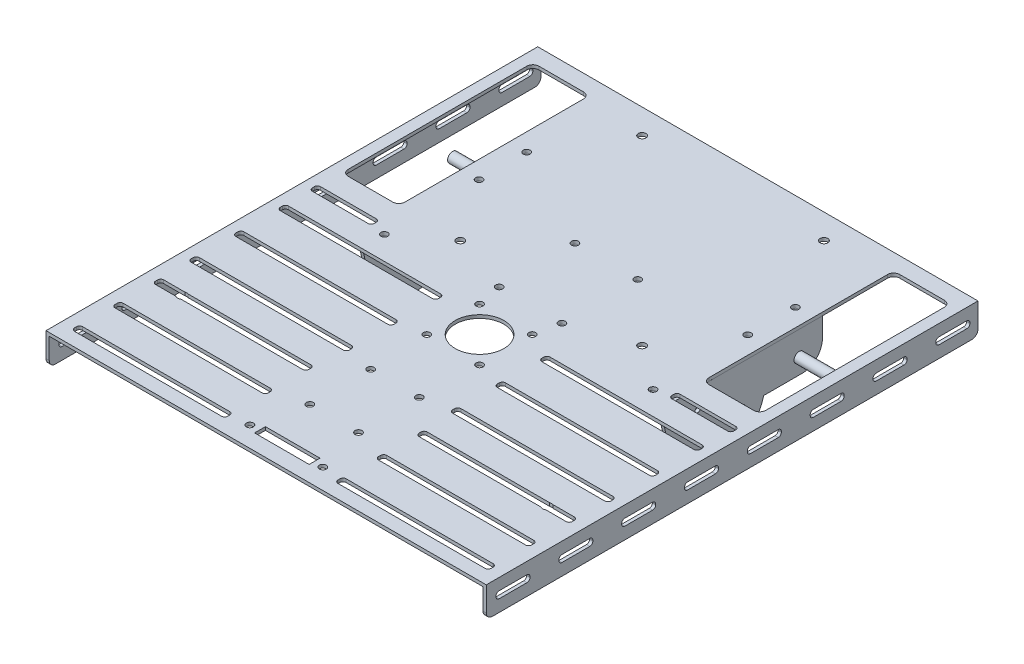
SolidWorks part; units mm, degrees
ref_plane "Front Plane" through (0, 0, 0) normal (0, 0, 1) x (1, 0, 0)
ref_plane "Top Plane" through (0, 0, 0) normal (0, 1, 0) x (1, 0, 0)
ref_plane "Right Plane" through (0, 0, 0) normal (1, 0, 0) x (0, 0, -1)
sketch "Sketch2" plane through (0, 0, 0) normal (0, 1, 0) x (1, 0, 0)
  line L7 (-172.2662, -88.2141) -> (41.7338, -88.2141)
  line L48 (-168.2662, 146.3841) -> (-140.2662, 146.3841)
  line L49 (-168.2662, 146.3841) -> (-168.2662, 52.2603)
  line L50 (-168.2662, 52.2603) -> (-140.2662, 52.2603)
  line L51 (-140.2662, 146.3841) -> (-140.2662, 52.2603)
  line L72 (41.7338, 154.3841) -> (-172.2662, 154.3841)
  line L75 (-65.2662, 154.3841) -> (-65.2662, -88.2141) construction
  line L76 (41.7338, -88.2141) -> (41.7338, 154.3841)
  line L77 (9.7338, 146.3841) -> (9.7338, 52.2603)
  line L78 (37.7338, 52.2603) -> (9.7338, 52.2603)
  line L79 (-172.2662, -88.2141) -> (-172.2662, 154.3841)
  line L80 (37.7338, 146.3841) -> (37.7338, 52.2603)
  line L81 (37.7338, 146.3841) -> (9.7338, 146.3841)
  point P2 (-154.2662, 146.3841)
  dimension "D1" = 8
  dimension "D3" = 4
  dimension "D6" = 107
  dimension "D9" = 28
extrude "Boss-Extrude1" add sketch "Sketch2" along normal blind 1.6
ref_plane "Plane3" through (-65.2662, 0, 0) normal (-1, 0, 0) x (0, 0, 1)
sketch "Sketch4" plane through (0, 0, 0) normal (0, -1, 0) x (1, 0, 0)
  line L5 (-172.2662, 15.9553) -> (41.7338, 15.9553) construction
  line L6 (-172.2662, -154.3841) -> (-172.2662, 88.2141) construction
  line L7 (41.7338, 88.2141) -> (41.7338, -154.3841) construction
  point P6 (-65.2662, 15.9553)
  line B0 (-140.2673, -111.2297) -> (-140.2673, -31.6718)
  line B1 (-140.2673, -111.2297) -> (-127.4267, -111.2297)
  line B2 (-140.2673, -31.6718) -> (-127.4299, -31.6718)
  line B3 (-76.7662, -37.9313) -> (-76.7662, -84.2325)
  line B4 (-76.7662, -37.9313) -> (-85.1807, -37.9313)
  line B5 (-76.7662, -84.2325) -> (-85.1807, -84.2325)
  line B6 (-122.4299, -36.6718) -> (-122.4299, -60.4336)
  line B7 (-122.4299, -60.4336) -> (-85.1807, -60.4336)
  line B8 (-85.1807, -60.4336) -> (-85.1807, -37.9313)
  line B9 (-85.1807, -84.2325) -> (-85.1807, -67.1203)
  line B10 (-85.1807, -67.1203) -> (-122.4267, -67.1203)
  line B11 (-122.4267, -67.1203) -> (-122.4267, -106.2297)
  arc B12 (-127.4299, -31.6718) -> (-122.4299, -36.6718) centre (-127.4299, -36.6718) cw
  arc B13 (-127.4267, -111.2297) -> (-122.4267, -106.2297) centre (-127.4267, -106.2297) ccw
  dimension "D1" = 11.5
sketch_block_instance "Block1-1"
sketch_block "Block1" parameters "D1"=5
extrude "Boss-Extrude3" add sketch "Sketch4" along normal blind 1.6129 separate body
sketch "Sketch6" plane through (-140.2673, 113.8349, 0) normal (1, 0, 0) x (0, -1, 0)
  line L1 (113.8349, 31.6718) -> (113.8349, 111.2297)
  line L7 (123.4041, 111.2297) -> (113.8349, 111.2297)
  line L8 (113.8349, 52.2603) -> (113.8349, 146.3841) construction
  line L10 (115.4478, 111.2297) -> (113.8349, 111.2297) construction
  line L11 (133.4041, 101.2297) -> (133.4041, 82.2567)
  line L13 (132.4365, 35.6062) -> (115.4478, 31.6718)
  line L14 (115.4478, 31.6718) -> (113.8349, 31.6718)
  circle A2 centre (133.4041, 71.8386) radius 1.27
  circle A4 centre (133.4041, 49.6644) radius 3
  circle A5 centre (125.8349, 99.7882) radius 2.55
  circle A6 centre (123.1933, 49.6644) radius 1.27
  circle A8 centre (143.6149, 49.6644) radius 1.27
  arc A10 (133.4041, 82.2567) -> (132.4365, 35.6062) centre (127.5185, 59.0435) cw
  arc A11 (133.4041, 101.2297) -> (123.4041, 111.2297) centre (123.4041, 101.2297) ccw
  line M25 (113.8349, 31.6718) -> (113.8349, 111.2297)
  line M26 (113.8349, 111.2297) -> (115.4478, 111.2297)
  line M27 (115.4478, 111.2297) -> (115.4478, 31.6718)
  line M28 (115.4478, 31.6718) -> (113.8349, 31.6718)
  dimension "D1" = 5.1
  dimension "D4" = 6
  dimension "D5" = 10
  dimension "D2" = 12
extrude "Boss-Extrude4" add sketch "Sketch6" along normal blind 1.6129 contours M28 M25 M26 M27 | M27 | A6 A2 A4 A8 region at (-140.2673, -0.8064, -71.4508) region at (-140.2673, -15.5641, -67.9069)
sketch "Sketch7" plane through (0, 0, 0) normal (0, -1, 0) x (1, 0, 0)
  line L0 (-172.2662, 88.2141) -> (41.7338, 88.2141) construction
  line L1 (-65.2662, -5.0799) -> (-65.2662, -29.0799)
  line L48 (-65.2662, -1159.7859) -> (-65.2662, 48840.2141) construction
  line L49 (41.7338, -154.3841) -> (-172.2662, -154.3841) construction
  line L50 (-65.2662, 80.4578) -> (-65.2662, 75.1009)
  line L51 (-65.2662, 80.4578) -> (-78.7298, 80.4578)
  line L52 (-65.2662, 75.1009) -> (-78.7298, 75.1009)
  line L53 (-78.7298, 80.4578) -> (-78.7298, 75.1009)
  circle A0 centre (-131.5463, -83.1098) radius 1.7
  circle A1 centre (-131.5463, -36.3977) radius 1.7
  circle A2 centre (-80.7521, -42.2194) radius 1.7
  circle A3 centre (-80.7521, -79.6224) radius 1.7
  circle A4 centre (-131.5463, -106.6172) radius 1.7
  circle A5 centre (-110.1162, -52.4299) radius 1.9
  circle A6 centre (-110.1162, -142.1299) radius 1.9
  circle A7 centre (-155.2662, 39.5701) radius 2.25
  circle A8 centre (-78.2662, -4.0799) radius 1.7
  circle A9 centre (-78.2662, -30.0799) radius 1.7
  arc A11 (-65.2662, -5.0799) -> (-65.2662, -29.0799) centre (-65.2662, -17.0799) ccw
  circle A12 centre (-83.2662, 78.2141) radius 1.7
  circle A13 centre (-77.2662, 24.6349) radius 1.7
  circle A14 centre (-77.2662, 54.6349) radius 1.7
  point P38 (-65.2662, -154.3841)
  dimension "D3" = 3.4
  dimension "D4" = 3.4
  dimension "D5" = 3.4
  dimension "D6" = 3.4
  dimension "D1" = 3.4
  dimension "D2" = 3.8
  dimension "D8" = 3.8
  dimension "D9" = 4.5
  dimension "D12" = 3.4
  dimension "D13" = 3.4
  dimension "D14" = 12
  dimension "D20" = 3.4
  dimension "D23" = 3.4
  dimension "D24" = 3.4
  dimension "D22" = 10
  dimension "D25" = 30
  dimension "D15" = 13
  dimension "D19" = 12
  dimension "D21" = 18
  dimension "D11" = 89.7
  dimension "D17" = 13
  dimension "D18" = 26
  dimension "D7" = 92
  dimension "D16" = 44.85
  dimension "D10" = 90
  dimension "D28" = 35.35
extrude "Cut-Extrude1" cut sketch "Sketch7" against normal blind 10 and the other way blind 10
mirror "Mirror1" about plane through (-65.2662, 0, 0) normal (-1, 0, 0) of bodies 157 158 103
mirror "Mirror2" about plane through (-65.2662, 0, 0) normal (-1, 0, 0) of "Cut-Extrude1"
sketch "Sketch9" plane through (-140.2662, 0, 0) normal (1, 0, 0) x (0, 0, -1)
  circle A0 centre (99.7882, -12) radius 2.5
extrude "Boss-Extrude6" add sketch "Sketch9" along normal blind 169 and the other way blind 21 separate body
sketch "Sketch11" plane through (0, 1.6, 0) normal (0, 1, 0) x (1, 0, 0)
  line L0 (-172.2662, 154.3841) -> (-172.2662, -88.2141)
  line L1 (-172.2662, 154.3841) -> (-173.8662, 154.3841)
  line L2 (-172.2662, -88.2141) -> (-173.8662, -88.2141)
  line L3 (-173.8662, 154.3841) -> (-173.8662, -88.2141)
  line L4 (41.7338, 154.3841) -> (41.7338, -88.2141)
  line L5 (41.7338, 154.3841) -> (43.3338, 154.3841)
  line L6 (41.7338, -88.2141) -> (43.3338, -88.2141)
  line L7 (43.3338, 154.3841) -> (43.3338, -88.2141)
  dimension "D1" = 1.6
  dimension "D2" = 1.6
extrude "Boss-Extrude7" add sketch "Sketch11" against normal blind 15
sketch "Sketch12" plane through (0, 1.6, 0) normal (0, 1, 0) x (1, 0, 0)
  line L12 (-65.2662, -1088.2141) -> (-65.2662, 48911.7859) construction
  line L13 (-173.8662, -88.2141) -> (43.3338, -88.2141) construction
  line L78 (-167.2842, 24.8362) -> (-92.2703, 24.8362)
  line L79 (-168.7842, 23.3362) -> (-168.7842, 22.3362)
  line L80 (-90.7703, 23.3362) -> (-90.7703, 22.3362)
  line L81 (-167.2842, 20.8362) -> (-92.2703, 20.8362)
  line L98 (-166.5277, -37.4749) -> (-93.977, -37.4749)
  line L99 (-168.0277, -38.9749) -> (-168.0277, -39.9749)
  line L100 (-92.477, -38.9749) -> (-92.477, -39.9749)
  line L101 (-166.5277, -41.4749) -> (-93.977, -41.4749)
  line L134 (-167.2842, -1.1638) -> (-92.2703, -1.1638)
  line L135 (-90.7703, 1.3362) -> (-90.7703, 0.3362)
  line L136 (-167.2842, 2.8362) -> (-92.2703, 2.8362)
  line L137 (-168.7842, 1.3362) -> (-168.7842, 0.3362)
  line L138 (-167.2842, -23.1638) -> (-92.2703, -23.1638)
  line L139 (-90.7703, -20.6638) -> (-90.7703, -21.6638)
  line L140 (-167.2842, -19.1638) -> (-92.2703, -19.1638)
  line L141 (-168.7842, -20.6638) -> (-168.7842, -21.6638)
  line L142 (-166.5277, -57.4749) -> (-93.977, -57.4749)
  line L143 (-168.0277, -58.9749) -> (-168.0277, -59.9749)
  line L144 (-92.477, -58.9749) -> (-92.477, -59.9749)
  line L145 (-166.5277, -61.4749) -> (-93.977, -61.4749)
  line L146 (-166.5277, -77.4749) -> (-93.977, -77.4749)
  line L147 (-168.0277, -78.9749) -> (-168.0277, -79.9749)
  line L148 (-92.477, -78.9749) -> (-92.477, -79.9749)
  line L149 (-166.5277, -81.4749) -> (-93.977, -81.4749)
  line L150 (35.9953, -81.4749) -> (-36.5554, -81.4749)
  line L151 (-38.0554, -78.9749) -> (-38.0554, -79.9749)
  line L152 (37.4953, -78.9749) -> (37.4953, -79.9749)
  line L153 (35.9953, -77.4749) -> (-36.5554, -77.4749)
  line L154 (35.9953, -61.4749) -> (-36.5554, -61.4749)
  line L155 (-38.0554, -58.9749) -> (-38.0554, -59.9749)
  line L156 (37.4953, -58.9749) -> (37.4953, -59.9749)
  line L157 (35.9953, -57.4749) -> (-36.5554, -57.4749)
  line L158 (38.2518, -20.6638) -> (38.2518, -21.6638)
  line L159 (36.7518, -19.1638) -> (-38.2621, -19.1638)
  line L160 (-39.7621, -20.6638) -> (-39.7621, -21.6638)
  line L161 (36.7518, -23.1638) -> (-38.2621, -23.1638)
  line L162 (38.2518, 1.3362) -> (38.2518, 0.3362)
  line L163 (36.7518, 2.8362) -> (-38.2621, 2.8362)
  line L164 (-39.7621, 1.3362) -> (-39.7621, 0.3362)
  line L165 (36.7518, -1.1638) -> (-38.2621, -1.1638)
  line L166 (35.9953, -41.4749) -> (-36.5554, -41.4749)
  line L167 (-38.0554, -38.9749) -> (-38.0554, -39.9749)
  line L168 (37.4953, -38.9749) -> (37.4953, -39.9749)
  line L169 (35.9953, -37.4749) -> (-36.5554, -37.4749)
  line L170 (36.7518, 20.8362) -> (-38.2621, 20.8362)
  line L171 (-39.7621, 23.3362) -> (-39.7621, 22.3362)
  line L172 (38.2518, 23.3362) -> (38.2518, 22.3362)
  line L173 (36.7518, 24.8362) -> (-38.2621, 24.8362)
  line L174 (-167.6958, 41.0358) -> (-140.217, 41.0358)
  line L175 (-169.1958, 39.5358) -> (-169.1958, 38.5358)
  line L176 (-138.717, 39.5358) -> (-138.717, 38.5358)
  line L177 (-167.6958, 37.0358) -> (-140.217, 37.0358)
  line L178 (38.6634, 39.5358) -> (38.6634, 38.5358)
  line L179 (37.1634, 41.0358) -> (9.6846, 41.0358)
  line L180 (8.1846, 39.5358) -> (8.1846, 38.5358)
  line L181 (37.1634, 37.0358) -> (9.6846, 37.0358)
  arc A0 (-92.2703, 24.8362) -> (-90.7703, 23.3362) centre (-92.2703, 23.3362) cw
  arc A1 (-90.7703, 22.3362) -> (-92.2703, 20.8362) centre (-92.2703, 22.3362) cw
  arc A2 (-168.7842, 22.3362) -> (-167.2842, 20.8362) centre (-167.2842, 22.3362) ccw
  arc A3 (-168.7842, 23.3362) -> (-167.2842, 24.8362) centre (-167.2842, 23.3362) cw
  arc A4 (-90.7703, 0.3362) -> (-92.2703, -1.1638) centre (-92.2703, 0.3362) cw
  arc A5 (-92.2703, 2.8362) -> (-90.7703, 1.3362) centre (-92.2703, 1.3362) cw
  arc A6 (-168.7842, 1.3362) -> (-167.2842, 2.8362) centre (-167.2842, 1.3362) cw
  arc A7 (-168.7842, 0.3362) -> (-167.2842, -1.1638) centre (-167.2842, 0.3362) ccw
  arc A8 (-90.7703, -21.6638) -> (-92.2703, -23.1638) centre (-92.2703, -21.6638) cw
  arc A9 (-92.2703, -19.1638) -> (-90.7703, -20.6638) centre (-92.2703, -20.6638) cw
  arc A10 (-168.7842, -20.6638) -> (-167.2842, -19.1638) centre (-167.2842, -20.6638) cw
  arc A11 (-168.7842, -21.6638) -> (-167.2842, -23.1638) centre (-167.2842, -21.6638) ccw
  arc A12 (-93.977, -37.4749) -> (-92.477, -38.9749) centre (-93.977, -38.9749) cw
  arc A13 (-92.477, -39.9749) -> (-93.977, -41.4749) centre (-93.977, -39.9749) cw
  arc A14 (-168.0277, -39.9749) -> (-166.5277, -41.4749) centre (-166.5277, -39.9749) ccw
  arc A15 (-168.0277, -38.9749) -> (-166.5277, -37.4749) centre (-166.5277, -38.9749) cw
  arc A32 (-93.977, -57.4749) -> (-92.477, -58.9749) centre (-93.977, -58.9749) cw
  arc A33 (-92.477, -59.9749) -> (-93.977, -61.4749) centre (-93.977, -59.9749) cw
  arc A34 (-168.0277, -59.9749) -> (-166.5277, -61.4749) centre (-166.5277, -59.9749) ccw
  arc A35 (-168.0277, -58.9749) -> (-166.5277, -57.4749) centre (-166.5277, -58.9749) cw
  arc A36 (-93.977, -77.4749) -> (-92.477, -78.9749) centre (-93.977, -78.9749) cw
  arc A37 (-92.477, -79.9749) -> (-93.977, -81.4749) centre (-93.977, -79.9749) cw
  arc A38 (-168.0277, -79.9749) -> (-166.5277, -81.4749) centre (-166.5277, -79.9749) ccw
  arc A39 (-168.0277, -78.9749) -> (-166.5277, -77.4749) centre (-166.5277, -78.9749) cw
  arc A40 (37.4953, -78.9749) -> (35.9953, -77.4749) centre (35.9953, -78.9749) ccw
  arc A41 (37.4953, -79.9749) -> (35.9953, -81.4749) centre (35.9953, -79.9749) cw
  arc A42 (-38.0554, -79.9749) -> (-36.5554, -81.4749) centre (-36.5554, -79.9749) ccw
  arc A43 (-36.5554, -77.4749) -> (-38.0554, -78.9749) centre (-36.5554, -78.9749) ccw
  arc A44 (37.4953, -58.9749) -> (35.9953, -57.4749) centre (35.9953, -58.9749) ccw
  arc A45 (37.4953, -59.9749) -> (35.9953, -61.4749) centre (35.9953, -59.9749) cw
  arc A46 (-38.0554, -59.9749) -> (-36.5554, -61.4749) centre (-36.5554, -59.9749) ccw
  arc A47 (-36.5554, -57.4749) -> (-38.0554, -58.9749) centre (-36.5554, -58.9749) ccw
  arc A48 (37.4953, -38.9749) -> (35.9953, -37.4749) centre (35.9953, -38.9749) ccw
  arc A49 (37.4953, -39.9749) -> (35.9953, -41.4749) centre (35.9953, -39.9749) cw
  arc A50 (-38.0554, -39.9749) -> (-36.5554, -41.4749) centre (-36.5554, -39.9749) ccw
  arc A51 (-36.5554, -37.4749) -> (-38.0554, -38.9749) centre (-36.5554, -38.9749) ccw
  arc A52 (38.2518, -21.6638) -> (36.7518, -23.1638) centre (36.7518, -21.6638) cw
  arc A53 (38.2518, -20.6638) -> (36.7518, -19.1638) centre (36.7518, -20.6638) ccw
  arc A54 (-38.2621, -19.1638) -> (-39.7621, -20.6638) centre (-38.2621, -20.6638) ccw
  arc A55 (-39.7621, -21.6638) -> (-38.2621, -23.1638) centre (-38.2621, -21.6638) ccw
  arc A56 (38.2518, 0.3362) -> (36.7518, -1.1638) centre (36.7518, 0.3362) cw
  arc A57 (38.2518, 1.3362) -> (36.7518, 2.8362) centre (36.7518, 1.3362) ccw
  arc A58 (-38.2621, 2.8362) -> (-39.7621, 1.3362) centre (-38.2621, 1.3362) ccw
  arc A59 (-39.7621, 0.3362) -> (-38.2621, -1.1638) centre (-38.2621, 0.3362) ccw
  arc A60 (38.2518, 23.3362) -> (36.7518, 24.8362) centre (36.7518, 23.3362) ccw
  arc A61 (38.2518, 22.3362) -> (36.7518, 20.8362) centre (36.7518, 22.3362) cw
  arc A62 (-39.7621, 22.3362) -> (-38.2621, 20.8362) centre (-38.2621, 22.3362) ccw
  arc A63 (-38.2621, 24.8362) -> (-39.7621, 23.3362) centre (-38.2621, 23.3362) ccw
  arc A64 (-140.217, 41.0358) -> (-138.717, 39.5358) centre (-140.217, 39.5358) cw
  arc A65 (-138.717, 38.5358) -> (-140.217, 37.0358) centre (-140.217, 38.5358) cw
  arc A66 (-169.1958, 38.5358) -> (-167.6958, 37.0358) centre (-167.6958, 38.5358) ccw
  arc A67 (-169.1958, 39.5358) -> (-167.6958, 41.0358) centre (-167.6958, 39.5358) cw
  arc A68 (38.6634, 38.5358) -> (37.1634, 37.0358) centre (37.1634, 38.5358) cw
  arc A69 (38.6634, 39.5358) -> (37.1634, 41.0358) centre (37.1634, 39.5358) ccw
  arc A70 (9.6846, 41.0358) -> (8.1846, 39.5358) centre (9.6846, 39.5358) ccw
  arc A71 (8.1846, 38.5358) -> (9.6846, 37.0358) centre (9.6846, 38.5358) ccw
  point P41 (-65.2662, -88.2141)
  point P42 (-92.477, -37.4749)
  point P45 (-92.477, -41.4749)
  point P48 (-168.0277, -41.4749)
  point P51 (-168.0277, -37.4749)
  point P55 (-90.7703, 24.8362)
  point P58 (-90.7703, 20.8362)
  point P61 (-168.7842, 20.8362)
  point P64 (-168.7842, 24.8362)
  point P157 (38.2518, 24.8362)
  point P158 (38.2518, 20.8362)
  point P159 (-39.7621, 20.8362)
  point P160 (-39.7621, 24.8362)
  point P161 (37.4953, -37.4749)
  point P162 (37.4953, -41.4749)
  point P163 (-38.0554, -41.4749)
  point P164 (-38.0554, -37.4749)
  dimension "D1" = 1.5
  dimension "D3" = 1.5
  dimension "D2" = 3
  dimension "D4" = 3
extrude "Cut-Extrude2" cut sketch "Sketch12" against normal blind 8
sketch "Sketch13" plane through (-173.8662, 0, 0) normal (-1, 0, 0) x (0, 0, 1)
  line L0 (-148.8578, -4.1114) -> (-135.1046, -4.1114)
  line L1 (-150.3578, -5.6114) -> (-150.3578, -6.0114)
  line L2 (-133.6046, -5.6114) -> (-133.6046, -6.0114)
  line L3 (-148.8578, -7.5114) -> (-135.1046, -7.5114)
  line L4 (-102.6046, -5.6114) -> (-102.6046, -6.0114)
  line L5 (-117.8578, -7.5114) -> (-104.1046, -7.5114)
  line L6 (-119.3578, -5.6114) -> (-119.3578, -6.0114)
  line L7 (-117.8578, -4.1114) -> (-104.1046, -4.1114)
  line L8 (-71.6046, -5.6114) -> (-71.6046, -6.0114)
  line L9 (-86.8578, -7.5114) -> (-73.1046, -7.5114)
  line L10 (-88.3578, -5.6114) -> (-88.3578, -6.0114)
  line L11 (-86.8578, -4.1114) -> (-73.1046, -4.1114)
  line L12 (-40.6046, -5.6114) -> (-40.6046, -6.0114)
  line L13 (-55.8578, -7.5114) -> (-42.1046, -7.5114)
  line L14 (-57.3578, -5.6114) -> (-57.3578, -6.0114)
  line L15 (-55.8578, -4.1114) -> (-42.1046, -4.1114)
  line L16 (-9.6046, -5.6114) -> (-9.6046, -6.0114)
  line L17 (-24.8578, -7.5114) -> (-11.1046, -7.5114)
  line L18 (-26.3578, -5.6114) -> (-26.3578, -6.0114)
  line L19 (-24.8578, -4.1114) -> (-11.1046, -4.1114)
  line L20 (21.3954, -5.6114) -> (21.3954, -6.0114)
  line L21 (6.1422, -7.5114) -> (19.8954, -7.5114)
  line L22 (4.6422, -5.6114) -> (4.6422, -6.0114)
  line L23 (6.1422, -4.1114) -> (19.8954, -4.1114)
  line L24 (52.3954, -5.6114) -> (52.3954, -6.0114)
  line L25 (37.1422, -7.5114) -> (50.8954, -7.5114)
  line L26 (35.6422, -5.6114) -> (35.6422, -6.0114)
  line L27 (37.1422, -4.1114) -> (50.8954, -4.1114)
  line L28 (83.3954, -5.6114) -> (83.3954, -6.0114)
  line L29 (68.1422, -7.5114) -> (81.8954, -7.5114)
  line L30 (66.6422, -5.6114) -> (66.6422, -6.0114)
  line L31 (68.1422, -4.1114) -> (81.8954, -4.1114)
  arc A0 (-150.3578, -6.0114) -> (-148.8578, -7.5114) centre (-148.8578, -6.0114) ccw
  arc A1 (-133.6046, -6.0114) -> (-135.1046, -7.5114) centre (-135.1046, -6.0114) cw
  arc A2 (-135.1046, -4.1114) -> (-133.6046, -5.6114) centre (-135.1046, -5.6114) cw
  arc A3 (-150.3578, -5.6114) -> (-148.8578, -4.1114) centre (-148.8578, -5.6114) cw
  arc A4 (-102.6046, -6.0114) -> (-104.1046, -7.5114) centre (-104.1046, -6.0114) cw
  arc A5 (-119.3578, -6.0114) -> (-117.8578, -7.5114) centre (-117.8578, -6.0114) ccw
  arc A6 (-119.3578, -5.6114) -> (-117.8578, -4.1114) centre (-117.8578, -5.6114) cw
  arc A7 (-104.1046, -4.1114) -> (-102.6046, -5.6114) centre (-104.1046, -5.6114) cw
  arc A8 (-71.6046, -6.0114) -> (-73.1046, -7.5114) centre (-73.1046, -6.0114) cw
  arc A9 (-88.3578, -6.0114) -> (-86.8578, -7.5114) centre (-86.8578, -6.0114) ccw
  arc A10 (-88.3578, -5.6114) -> (-86.8578, -4.1114) centre (-86.8578, -5.6114) cw
  arc A11 (-73.1046, -4.1114) -> (-71.6046, -5.6114) centre (-73.1046, -5.6114) cw
  arc A12 (-40.6046, -6.0114) -> (-42.1046, -7.5114) centre (-42.1046, -6.0114) cw
  arc A13 (-57.3578, -6.0114) -> (-55.8578, -7.5114) centre (-55.8578, -6.0114) ccw
  arc A14 (-57.3578, -5.6114) -> (-55.8578, -4.1114) centre (-55.8578, -5.6114) cw
  arc A15 (-42.1046, -4.1114) -> (-40.6046, -5.6114) centre (-42.1046, -5.6114) cw
  arc A16 (-9.6046, -6.0114) -> (-11.1046, -7.5114) centre (-11.1046, -6.0114) cw
  arc A17 (-26.3578, -6.0114) -> (-24.8578, -7.5114) centre (-24.8578, -6.0114) ccw
  arc A18 (-26.3578, -5.6114) -> (-24.8578, -4.1114) centre (-24.8578, -5.6114) cw
  arc A19 (-11.1046, -4.1114) -> (-9.6046, -5.6114) centre (-11.1046, -5.6114) cw
  arc A20 (21.3954, -6.0114) -> (19.8954, -7.5114) centre (19.8954, -6.0114) cw
  arc A21 (4.6422, -6.0114) -> (6.1422, -7.5114) centre (6.1422, -6.0114) ccw
  arc A22 (4.6422, -5.6114) -> (6.1422, -4.1114) centre (6.1422, -5.6114) cw
  arc A23 (19.8954, -4.1114) -> (21.3954, -5.6114) centre (19.8954, -5.6114) cw
  arc A24 (52.3954, -6.0114) -> (50.8954, -7.5114) centre (50.8954, -6.0114) cw
  arc A25 (35.6422, -6.0114) -> (37.1422, -7.5114) centre (37.1422, -6.0114) ccw
  arc A26 (35.6422, -5.6114) -> (37.1422, -4.1114) centre (37.1422, -5.6114) cw
  arc A27 (50.8954, -4.1114) -> (52.3954, -5.6114) centre (50.8954, -5.6114) cw
  arc A28 (83.3954, -6.0114) -> (81.8954, -7.5114) centre (81.8954, -6.0114) cw
  arc A29 (66.6422, -6.0114) -> (68.1422, -7.5114) centre (68.1422, -6.0114) ccw
  arc A30 (66.6422, -5.6114) -> (68.1422, -4.1114) centre (68.1422, -5.6114) cw
  arc A31 (81.8954, -4.1114) -> (83.3954, -5.6114) centre (81.8954, -5.6114) cw
  dimension "D1" = 1.5
  dimension "D2" = 8
extrude "Cut-Extrude3" cut sketch "Sketch13" against normal blind 222
fillet "Fillet1" radius 3 12 edges at (-173.0662, -13.4, 88.2141) (-173.0662, -13.4, -154.3841) (42.5338, -13.4, -154.3841) (42.5338, -13.4, 88.2141) (-140.2662, 0.8, -52.2603) (-168.2662, 0.8, -146.3841) (-168.2662, 0.8, -52.2603) (-140.2662, 0.8, -146.3841) (37.7338, 0.8, -146.3841) (9.7338, 0.8, -146.3841) (37.7338, 0.8, -52.2603) (9.7338, 0.8, -52.2603)
equation "\"hardboard_width\"= 3.175"
equation "\"D1@Boss-Extrude1\"=\"hardboard_width\""
equation "\"steel_24g_thickness\"= 0.5"
equation "\"m3_clearance_hole\"= 3.4"
equation "\"D3@Sketch7\"=\"m3_clearance_hole\""
equation "\"D4@Sketch7\"=\"m3_clearance_hole\""
equation "\"D5@Sketch7\"=\"m3_clearance_hole\""
equation "\"D6@Sketch7\"=\"m3_clearance_hole\""
equation "\"steel_16g_thickness\"=1.6129"
equation "\"D1@Boss-Extrude3\"=\"steel_16g_thickness\""
equation "\"D1@Boss-Extrude4\"=\"steel_16g_thickness\""
equation "\"D1@Sketch7\"=\"m3_clearance_hole\""
equation "\"D12@Sketch7\"=\"m3_clearance_hole\""
equation "\"D20@Sketch7\"=\"m3_clearance_hole\""
equation "\"D23@Sketch7\"=\"m3_clearance_hole\""
equation "\"D24@Sketch7\"=\"m3_clearance_hole\""
equation "\"D13@Sketch7\"=\"m3_clearance_hole\""
equation "\"D28@Sketch7\"=80.2-44.85"
